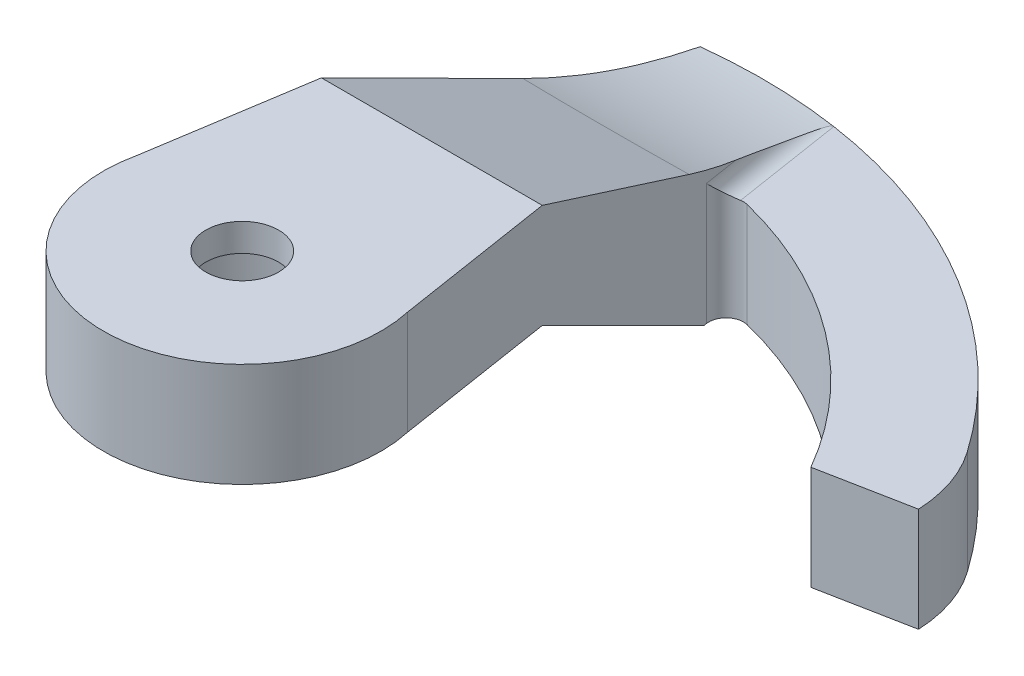
SolidWorks part; units mm, degrees
material "PEI"
ref_plane "Front Plane" through (0, 0, 0) normal (0, 0, 1) x (1, 0, 0)
ref_plane "Top Plane" through (0, 0, 0) normal (0, 1, 0) x (1, 0, 0)
ref_plane "Right Plane" through (0, 0, 0) normal (1, 0, 0) x (0, 0, -1)
sketch "Sketch1" plane through (0, 0, 0) normal (0, 1, 0) x (1, 0, 0)
  circle A0 centre (0, 0) radius 4
  circle A1 centre (0, 0) radius 1.05
  dimension "D1" = 8
  dimension "D2" = 2.1
extrude "Boss-Extrude1" add sketch "Sketch1" along normal blind 0.5
sketch "Sketch2" plane through (0, 0, 0) normal (0, -1, 0) x (-1, 0, 0)
  circle A0 centre (0, 0) radius 4
  circle A1 centre (0, 0) radius 2.45
  circle A3 centre (0, 0) radius 4 construction
  dimension "D1" = 4.9
extrude "Boss-Extrude2" add sketch "Sketch2" along normal blind 2.5
sketch "Sketch3" plane through (0, 0.5, 0) normal (0, 1, 0) x (1, 0, 0)
  line L0 (-3.9052, 0.8656) -> (-2, 13)
  line L1 (-2, 13) -> (2, 13)
  line L2 (2, 13) -> (3.9052, 0.8656)
  line L3 (0, 0) -> (-6.544, 0) construction
  circle A0 centre (0, 0) radius 4 construction
  arc A1 (-3.9052, 0.8656) -> (3.9052, 0.8656) centre (0, 0) cw
  point P7 (0, 4)
  point P9 (0, 13)
  dimension "D1" = 4
  dimension "D2" = 9
  dimension "D5" = 0.8656
extrude "Brazo" add sketch "Sketch3" against normal blind 6.2
ref_plane "Plane1" through (0, 0, -0.8656) normal (0, 0, 1) x (1, 0, 0)
sketch "Sketch4" plane through (0, 0, -0.8656) normal (0, 0, 1) x (1, 0, 0)
  line L0 (-3.9052, -5.7) -> (-3.9052, -2.5)
  line L1 (-3.9052, -2.5) -> (3.9052, -2.5)
  line L2 (3.9052, -2.5) -> (3.9052, -5.7)
  line L3 (3.9052, -5.7) -> (-3.9052, -5.7)
extrude "Corte de exedente" cut sketch "Sketch4" against normal blind 1.6
sketch "Sketch5" plane through (0, 0, 0) normal (1, 0, 0) x (0, 0, -1)
  line L0 (2.4656, -2.5) -> (5.4656, -2.5)
  line L1 (5.4656, -2.5) -> (11, -5.7)
  line L2 (2.4656, -5.7) -> (13, -5.7) construction
  line L3 (11, -5.7) -> (2.4656, -5.7)
  line L4 (2.4656, -5.7) -> (2.4656, -2.5)
  line L5 (13, -5.7) -> (13, 0.5) construction
  line L6 (5.4656, 0.5) -> (13, 0.5)
  line L7 (13, 0.5) -> (0.8656, 0.5) construction
  line L8 (13, 0.5) -> (13, -2.7)
  line L9 (13, -5.7) -> (13, 0.5) construction
  line L10 (13, -2.7) -> (5.4656, 0.5)
  line L11 (13, -5.7) -> (2.4656, -5.7) construction
  dimension "D1" = 2
  dimension "D2" = 3
  dimension "D3" = 30.037
  dimension "D4" = 3
extrude "Corte Inferior" cut sketch "Sketch5" against normal mid plane 13
sketch "Sketch7" plane through (0, -5.7, 0) normal (0, 1, 0) x (1, 0, 0)
  line L0 (-3.183, 5.4656) -> (-3.9052, 0.8656) construction
  line L1 (-2.1886, 11.7987) -> (-1.7012, 14.9032)
  line L2 (0, 0) -> (10.9941, 0) construction
  line L3 (0, 0) -> (13.5266, 7.8096) construction
  line L4 (10.3923, 6) -> (12.9901, 6.505)
  line L5 (12.9904, 7.5) -> (12.9901, 6.505)
  arc A0 (-2.1886, 11.7987) -> (10.3923, 6) centre (0, 0) cw
  arc A1 (-1.7012, 14.9032) -> (12.9904, 7.5) centre (0, 0) cw
  dimension "D1" = 12
  dimension "D2" = 3
  dimension "D3" = 30
  dimension "D4" = 19
extrude "Boss-Extrude4" add sketch "Sketch7" along normal blind 3 contours A1 L5 L4 A0 L1
fillet "Fillet1" radius 4 1 edges at (12.9904, -4.2, -7.5)
fillet "Fillet2" radius 14 1 edges at (0, -2.7, -13)
fillet "Fillet3" radius 0.5 2 edges at (1.9449, -2.7, -13.351) (2.1886, -4.2, -11.7987)
sketch "Sketch8" plane through (0, 0, 0) normal (0, -1, 0) x (-1, 0, 0)
  circle A0 centre (0, 0) radius 2.45
  circle A1 centre (0, 0) radius 1.05
extrude "Boss-Extrude5" add sketch "Sketch8" along normal blind 0.3
